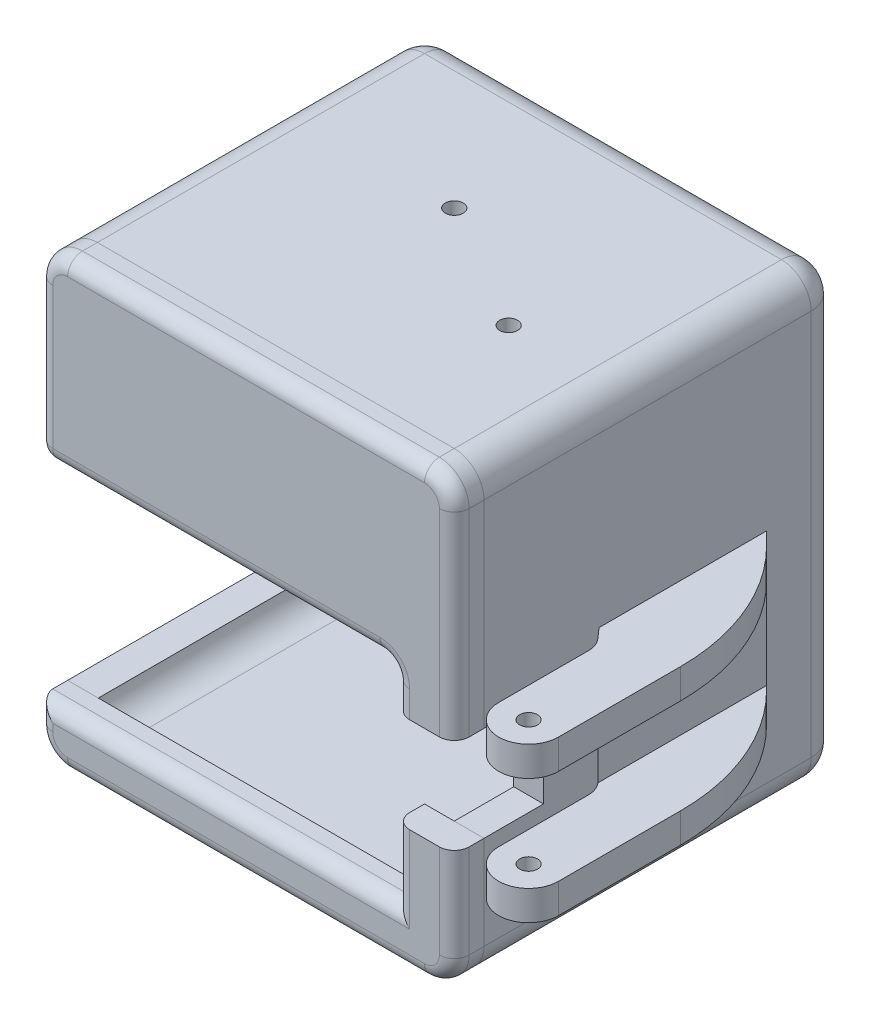
SolidWorks part; units mm, degrees
ref_plane "Alzado" through (0, 0, 0) normal (1, 0, 0) x (0, 1, 0)
ref_plane "Planta" through (0, 0, 0) normal (0, 0, 1) x (0, 1, 0)
ref_plane "Vista lateral" through (0, 0, 0) normal (0, 1, 0) x (-1, 0, 0)
sketch "Croquis2" plane through (0, 0, 0) normal (0, 0, 1) x (0, 1, 0)
  line L1 (-81.5709, -80.0129) -> (68.4291, -80.0129)
  line L2 (-81.5709, -80.0129) -> (-81.5709, 59.9871)
  line L3 (-81.5709, 59.9871) -> (68.4291, 59.9871)
  line L4 (68.4291, -80.0129) -> (68.4291, 59.9871)
  line L5 (-81.5709, -80.0129) -> (68.4291, 59.9871) construction
  line L6 (-81.5709, 59.9871) -> (68.4291, -80.0129) construction
  point P0 (-6.5709, -10.0129)
  dimension "D1" = 150
  dimension "D2" = 140
extrude "Saliente-Extruir1" add sketch "Croquis2" along normal blind 70 and the other way blind 50
shell "Vaciado1" thickness 10 removed face at (10.0129, -6.5709, 70)
sketch "Croquis4" plane through (0, 0, 0) normal (0, 1, 0) x (-1, 0, 0)
  line L0 (35.3553, 35.3553) -> (0, 0) construction
  line L1 (0, 0) -> (59.9871, 0) construction
  line L3 (59.9871, -50) -> (59.9871, 70) construction
  line L5 (0, 0) -> (0, 50) construction
  line L7 (0, 0) -> (-43.3013, 25) construction
  circle A0 centre (0, 0) radius 3
  circle A1 centre (-50, 0) radius 3 construction
  circle A2 centre (35.3553, 35.3553) radius 3 construction
  circle A3 centre (-43.3013, 25) radius 3
  dimension "D4" = 6
  dimension "D1" = 50
  dimension "D2" = 45
  dimension "D3" = 50
  dimension "D6" = 50
  dimension "D7" = 60
extrude "Cortar-Extruir1" cut sketch "Croquis4" against normal through all both and the other way through all
sketch "Croquis5" [suppressed] plane through (0, 0, 0) normal (0, 1, 0) x (-1, 0, 0)
  line L2 (-70.0129, -40) -> (59.9871, -40)
  line L3 (-80.0129, -50) -> (59.9871, -50) construction
  line L4 (59.9871, -50) -> (59.9871, 70)
  line L5 (59.9871, 70) -> (-80.0129, 70)
  line L6 (-80.0129, 70) -> (-80.0129, -50)
  line L7 (-80.0129, -50) -> (59.9871, -50)
  line L8 (59.9871, -40) -> (59.9871, 70)
  line L9 (59.9871, 70) -> (-70.0129, 70)
  line L10 (-70.0129, 70) -> (-70.0129, -40)
  line L12 (-80.0129, 70) -> (59.9871, 70) construction
  line L13 (-80.0129, -50) -> (-80.0129, 70) construction
  dimension "D3" = 10
extrude "Cortar-Extruir2" [suppressed] cut sketch "Croquis5" along normal offset from surface 10 and the other way offset from surface 10
fillet "Redondeo9" radius 10 12 edges at (-59.9871, -6.5709, -50) (-59.9871, 68.4291, 10) (10.0129, -81.5709, -50) (-59.9871, -81.5709, 10) (80.0129, -6.5709, -50) (80.0129, -81.5709, 10) (80.0129, 68.4291, 10) (10.0129, 68.4291, -50) (70.0129, 58.4291, 15) (70.0129, -71.5709, 15) (-49.9871, 58.4291, 15) (-49.9871, -71.5709, 15)
sketch "Croquis6" plane through (0, 0, 70) normal (0, 0, 1) x (1, 0, 0)
  line L0 (-59.9871, 58.4291) -> (-59.9871, -71.5709) construction
  line L1 (-59.9871, -64.0709) -> (70.0129, -64.0709)
  line L2 (-59.9871, -64.0709) -> (-59.9871, 5.9291)
  line L3 (-59.9871, 5.9291) -> (70.0129, 5.9291)
  line L4 (70.0129, -64.0709) -> (70.0129, 5.9291)
  line L7 (70.0129, -61.5709) -> (70.0129, 48.4291) construction
  line L8 (-49.9871, -81.5709) -> (70.0129, -81.5709) construction
  dimension "D1" = 17.5
  dimension "D2" = 70
extrude "Cortar-Extruir3" cut sketch "Croquis6" against normal blind 100
sketch "Croquis7" plane through (0, 0, 70) normal (0, 0, 1) x (1, 0, 0)
  line L1 (60.0129, 5.9291) -> (60.0129, -8.0709)
  line L3 (-59.9871, -64.0709) -> (60.0129, -64.0709)
  line L4 (-59.9871, 5.9291) -> (60.0129, 5.9291)
  line L6 (-49.9871, -81.5709) -> (70.0129, -81.5709) construction
  line L7 (80.0129, -71.5709) -> (80.0129, 58.4291) construction
  line L8 (70.0129, 68.4291) -> (-49.9871, 68.4291) construction
  line L11 (-49.9871, -81.5709) -> (70.0129, -81.5709)
  line L21 (80.0129, -71.5709) -> (80.0129, -40.0709)
  line L22 (70.0129, 68.4291) -> (-49.9871, 68.4291)
  line L37 (-59.9871, -64.0709) -> (-59.9871, -71.5709) construction
  line L43 (-59.9871, -64.0709) -> (-59.9871, -71.5709)
  line L44 (-59.9871, 58.4291) -> (-59.9871, 5.9291) construction
  line L45 (-59.9871, 58.4291) -> (-59.9871, 5.9291)
  line L46 (60.0129, -8.0709) -> (80.0129, -40.0709) construction
  line L47 (60.0129, -8.0709) -> (80.0129, -8.0709) construction
  line L49 (60.0129, -40.0709) -> (80.0129, -40.0709) construction
  line L51 (80.0129, -8.0709) -> (60.0129, -40.0709) construction
  line L52 (60.0129, -40.0709) -> (60.0129, -64.0709)
  line L53 (60.0129, -8.0709) -> (60.0129, -40.0709)
  line L55 (80.0129, -8.0709) -> (80.0129, 58.4291)
  line L56 (80.0129, -8.0709) -> (80.0129, -40.0709)
  arc A1 (70.0129, -81.5709) -> (80.0129, -71.5709) centre (70.0129, -71.5709) ccw construction
  arc A2 (80.0129, 58.4291) -> (70.0129, 68.4291) centre (70.0129, 58.4291) ccw construction
  arc A5 (70.0129, -81.5709) -> (80.0129, -71.5709) centre (70.0129, -71.5709) ccw
  arc A8 (80.0129, 58.4291) -> (70.0129, 68.4291) centre (70.0129, 58.4291) ccw
  arc A10 (-59.9871, -71.5709) -> (-49.9871, -81.5709) centre (-49.9871, -71.5709) ccw construction
  arc A11 (-59.9871, -71.5709) -> (-49.9871, -81.5709) centre (-49.9871, -71.5709) ccw
  arc A12 (-49.9871, 68.4291) -> (-59.9871, 58.4291) centre (-49.9871, 58.4291) ccw construction
  arc A13 (-49.9871, 68.4291) -> (-59.9871, 58.4291) centre (-49.9871, 58.4291) ccw
  point P3 (70.0129, -24.0709)
  dimension "D2" = 32
  dimension "D1" = 120
  dimension "D3" = 24
extrude "Saliente-Extruir2" add sketch "Croquis7" along normal blind 10 separate body
fillet "Redondeo17" radius 5 14 edges at (-59.9871, -67.8209, 80) (-57.0582, -78.642, 80) (10.0129, -81.5709, 80) (77.0839, -78.642, 80) (80.0129, -6.5709, 80) (77.0839, 65.5001, 80) (10.0129, 68.4291, 80) (-57.0582, 65.5001, 80) (-59.9871, 32.1791, 80) (60.0129, 5.9291, 75) (60.0129, -29.0709, 80) (0.0129, -64.0709, 80) (0.0129, 5.9291, 80) (-59.9871, 5.9291, 75)
ref_plane "Plano1" through (0, -24.0709, 0) normal (0, 1, 0) x (1, 0, 0)
sketch "Croquis8" plane through (0, -24.0709, 0) normal (0, 1, 0) x (1, 0, 0)
  line L0 (80.0129, 25) -> (84.5551, 20.4578)
  line L1 (80.0129, 40) -> (80.0129, -70) construction
  line L2 (105.0576, -29.0397) -> (105.0576, -70)
  line L3 (80.0129, -31.3206) -> (80.0129, 25)
  line L4 (84.9424, -70) -> (84.9424, -39.8077)
  line L5 (83.0213, -34.7286) -> (80.0129, -31.3206)
  circle A0 centre (95, -70) radius 3
  arc A1 (105.0576, -70) -> (84.9424, -70) centre (95, -70) cw
  arc A2 (84.9424, -39.8077) -> (83.0213, -34.7286) centre (77.2675, -39.8077) ccw
  arc A3 (84.5551, 20.4578) -> (105.0576, -29.0397) centre (35.0576, -29.0397) cw
  dimension "D1" = 6
  dimension "D9" = 70
  dimension "D3" = 70
  dimension "D5" = 25
  dimension "D6" = 45
  dimension "D2" = 95
extrude "Saliente-Extruir3" add sketch "Croquis8" along normal blind 10 from offset 16 separate body
mirror "Simetría1" about plane through (0, -24.0709, 0) normal (0, 1, 0) of bodies 106
sketch "Croquis10" plane through (0, -24.0709, 0) normal (0, 1, 0) x (1, 0, 0)
  line L8 (83.0213, -34.7286) -> (83.0213, 21.9916)
  line L13 (80.0129, 25) -> (80.0129, -31.3206)
  line L14 (80.0129, -31.3206) -> (83.0213, -34.7286)
  line L15 (84.9424, -39.8077) -> (84.9424, -70)
  line L16 (105.0576, -70) -> (105.0576, -29.0397)
  line L17 (84.5551, 20.4578) -> (80.0129, 25)
  line L18 (80.0129, 25) -> (80.0129, -31.3206)
  line L19 (80.0129, -31.3206) -> (83.0213, -34.7286)
  line L22 (83.0213, 21.9916) -> (80.0129, 25)
  arc A5 (84.9424, -39.8077) -> (83.0213, -34.7286) centre (77.2675, -39.8077) ccw
  arc A6 (84.9424, -70) -> (105.0576, -70) centre (95, -70) ccw
  arc A7 (105.0576, -29.0397) -> (84.5551, 20.4578) centre (35.0576, -29.0397) ccw
  dimension "D1" = 0
extrude "Saliente-Extruir4" add sketch "Croquis10" along normal mid plane 50
fillet "Redondeo14" [suppressed] radius 4
sketch "Croquis11" plane through (0, 0, 80) normal (0, 0, 1) x (1, 0, 0)
  line L0 (105.0576, -40.0709) -> (84.9424, -40.0709) construction
  line L1 (83.0213, -8.0709) -> (60.0129, -8.0709)
  line L2 (83.0213, -8.0709) -> (83.0213, -40.0709)
  line L3 (83.0213, -40.0709) -> (60.0129, -40.0709)
  line L4 (60.0129, -8.0709) -> (60.0129, -40.0709)
  line L5 (60.0129, -64.0709) -> (60.0129, 0.9291) construction
extrude "Cortar-Extruir4" cut sketch "Croquis11" against normal blind 30
equation "\"Zbarras\"= 50"
equation "\"angulo\"= 30"
equation "\"ancho_total_L1\"= 45"
equation "\"agujeros\"= 6"
equation "\"D6@Croquis4\"=\"Zbarras\""
equation "\"D4@Croquis4\"=\"agujeros\""
equation "\"esp\"= 10"
equation "\"D1@Cortar-Extruir2\"=\"esp\""
equation "\"D2@Cortar-Extruir2\"=\"esp\""
equation "\"D2@Croquis5\"=\"esp\""
equation "\"D3@Croquis5\"=\"D2@Croquis5\""
equation "\"D1@Vaciado1\"=\"esp\""
equation "\"D1@Saliente-Extruir2\"=\"esp\""
equation "\"D1@Croquis8\"=\"agujeros\""
equation "\"D1@Saliente-Extruir3\"=\"esp\""
equation "\"D19@Saliente-Extruir3\"=\"esp\"*1.5+1"
equation "\"D1@Cortar-Extruir4\"=\"esp\"*3"
